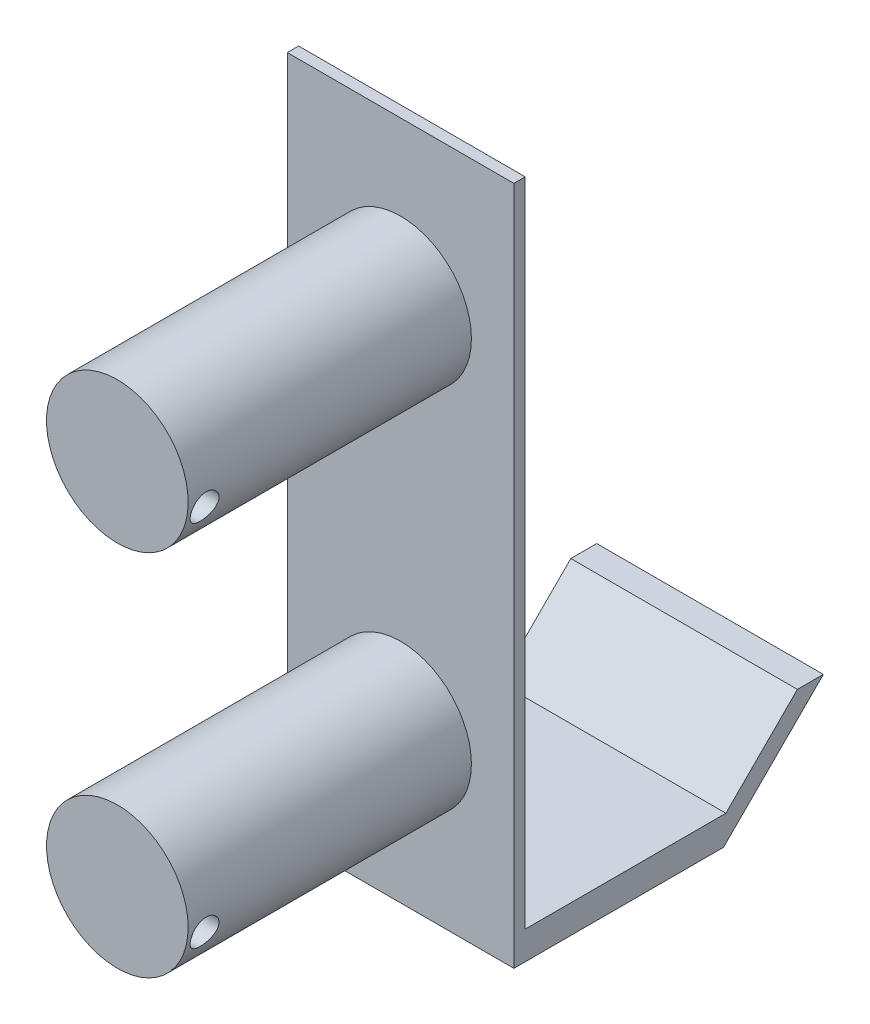
SolidWorks part; units mm, degrees
ref_plane "Front Plane" through (0, 0, 0) normal (0, 0, 1) x (1, 0, 0)
ref_plane "Top Plane" through (0, 0, 0) normal (0, 1, 0) x (1, 0, 0)
ref_plane "Right Plane" through (0, 0, 0) normal (1, 0, 0) x (0, 0, -1)
sketch "Sketch1" plane through (0, 0, 0) normal (0, 0, 1) x (1, 0, 0)
  line L1 (-25.4, 76.2) -> (25.4, 76.2)
  line L2 (-25.4, 76.2) -> (-25.4, -76.2)
  line L3 (-25.4, -76.2) -> (25.4, -76.2)
  line L4 (25.4, 76.2) -> (25.4, -76.2)
  line L5 (-25.4, 76.2) -> (25.4, -76.2) construction
  line L6 (-25.4, -76.2) -> (25.4, 76.2) construction
  point P0 (0, 0)
  dimension "D1" = 50.8
  dimension "D2" = 152.4
extrude "Boss-Extrude1" add sketch "Sketch1" along normal blind 2.54
sketch "Sketch2" plane through (0, 0, 2.54) normal (0, 0, 1) x (1, 0, 0)
  line L1 (-25.4, -76.2) -> (25.4, -76.2) construction
  circle A0 centre (0, 41.275) radius 15.875
  circle A1 centre (0, -41.275) radius 15.875
  dimension "D1" = 31.75
  dimension "D2" = 31.75
  dimension "D3" = 50.8
  dimension "D4" = 19.05
sketch "Sketch3" plane through (0, 0, 0) normal (0, 0, -1) x (-1, 0, 0)
  line L1 (-25.4, -69.85) -> (25.4, -69.85)
  line L2 (-25.4, -69.85) -> (-25.4, -76.2)
  line L3 (-25.4, -76.2) -> (25.4, -76.2)
  line L4 (25.4, -69.85) -> (25.4, -76.2)
  line L5 (-25.4, -69.85) -> (25.4, -76.2) construction
  line L6 (-25.4, -76.2) -> (25.4, -69.85) construction
  point P0 (0, -73.025)
  dimension "D1" = 6.35
extrude "Boss-Extrude3" add sketch "Sketch3" along normal blind 50.8
sketch "Sketch4" plane through (25.4, 0, 0) normal (1, 0, 0) x (0, 0, -1)
  line L0 (44.45, -76.2) -> (66.8321, -53.8179)
  line L1 (-2.54, -76.2) -> (50.8, -76.2) construction
  line L2 (50.8, -69.85) -> (50.8, -76.2) construction
  line L3 (38.6357, -76.2) -> (61.0178, -53.8179)
  line L4 (66.8321, -53.8179) -> (61.0178, -53.8179)
  line L5 (38.6357, -76.2) -> (44.45, -76.2)
  dimension "D1" = 45
extrude "Boss-Extrude4" add sketch "Sketch4" against normal up to surface (50.8 mm away) up to face at (-25.4, -23.2833, -16.0867)
extrude "Boss-Extrude5" add sketch "Sketch2" along normal blind 63.5
sketch "Sketch5" plane through (25.4, 0, 0) normal (1, 0, 0) x (0, 0, -1)
  line L0 (65.7134, -54.9366) -> (29.2671, -91.3829)
  line L1 (50.8, -69.85) -> (66.8321, -53.8179) construction
extrude "Cut-Extrude1" cut sketch "Sketch5" against normal through all and the other way through all
sketch "Sketch6" plane through (0, 0, 0) normal (1, 0, 0) x (0, 0, -1)
  line L0 (-2.54, -25.4) -> (-66.04, -25.4) construction
  line L1 (-2.54, 57.15) -> (-66.04, 57.15) construction
  circle A0 centre (-62.0263, 38.1) radius 3.175
  circle A1 centre (-62.0263, -44.45) radius 3.175
  dimension "D1" = 6.35
  dimension "D2" = 6.35
  dimension "D3" = 19.05
  dimension "D4" = 19.05
extrude "Cut-Extrude2" cut sketch "Sketch6" against normal through all both and the other way through all
